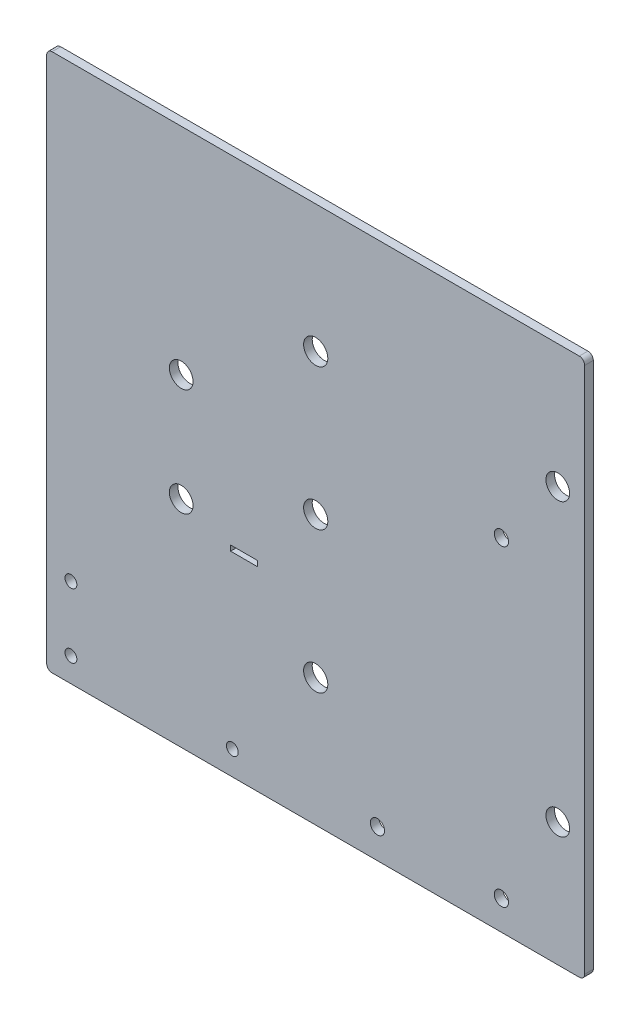
SolidWorks part; units mm, degrees
material "FR4_stuffedProtoboard"
ref_plane "Front Plane" through (0, 0, 0) normal (0, 0, 1) x (1, 0, 0)
ref_plane "Top Plane" through (0, 0, 0) normal (0, 1, 0) x (1, 0, 0)
ref_plane "Right Plane" through (0, 0, 0) normal (1, 0, 0) x (0, 0, -1)
sketch "Sketch1" plane through (0, 0, 0) normal (0, 0, 1) x (1, 0, 0)
  line L1 (-50, -50) -> (50, -50)
  line L2 (-50, -50) -> (-50, 50)
  line L3 (-50, 50) -> (50, 50)
  line L4 (50, -50) -> (50, 50)
  line L5 (-50, -50) -> (50, 50) construction
  line L6 (-50, 50) -> (50, -50) construction
  dimension "D1" = 100
extrude "Boss-Extrude1" add sketch "Sketch1" along normal blind 1.6
sketch "Sketch2" [suppressed] plane through (0, 0, 1.6) normal (0, 0, 1) x (1, 0, 0)
  circle A0 centre (0, 0) radius 50
  line M2 (50, -50) -> (50, 50)
  line M3 (50, 50) -> (-50, 50)
  line M4 (-50, 50) -> (-50, -50)
  line M5 (-50, -50) -> (50, -50)
  dimension "D1" = 100
extrude "Cut-Extrude1" [suppressed] cut sketch "Sketch2" against normal blind 1.6 contours A0 M3 M4 | A0 M4 M5 | A0 M5 M2 | A0 M2 M3
sketch "Sketch3" plane through (0, 0, 0) normal (0, 0, -1) x (-1, 0, 0)
  line L0 (-40, -22) -> (-50, -22) construction
  line L1 (-40, -32) -> (-40, -22) construction
  line L2 (-50, -32) -> (-40, -32) construction
  line L3 (-50, -22) -> (-50, -32) construction
  line L4 (-40, -22) -> (-50, -22)
  line L5 (-40, -32) -> (-40, -22)
  line L6 (-50, -32) -> (-40, -32)
  line L7 (-50, -22) -> (-50, -32)
  line L8 (-40, 22) -> (-40, 32) construction
  line L9 (-40, 32) -> (-50, 32) construction
  line L10 (-50, 32) -> (-50, 22) construction
  line L11 (-50, 22) -> (-40, 22) construction
  line L12 (-40, 22) -> (-40, 32)
  line L13 (-40, 32) -> (-50, 32)
  line L14 (-50, 32) -> (-50, 22)
  line L15 (-50, 22) -> (-40, 22)
  line L16 (5, -22) -> (-5, -22) construction
  line L17 (5, -32) -> (5, -22) construction
  line L18 (-5, -32) -> (5, -32) construction
  line L19 (-5, -22) -> (-5, -32) construction
  line L20 (5, -22) -> (-5, -22)
  line L21 (5, -32) -> (5, -22)
  line L22 (-5, -32) -> (5, -32)
  line L23 (-5, -22) -> (-5, -32)
  line L24 (5, 22) -> (5, 32) construction
  line L25 (5, 32) -> (-5, 32) construction
  line L26 (-5, 32) -> (-5, 22) construction
  line L27 (-5, 22) -> (5, 22) construction
  line L28 (5, 22) -> (5, 32)
  line L29 (5, 32) -> (-5, 32)
  line L30 (-5, 32) -> (-5, 22)
  line L31 (-5, 22) -> (5, 22)
  line L32 (17, 25) -> (45, 25) construction
  line L33 (45, 25) -> (45, -25) construction
  line L34 (17, -25) -> (45, -25) construction
  line L35 (17, 25) -> (17, -25) construction
  line L36 (17, 25) -> (45, 25)
  line L37 (45, 25) -> (45, -25)
  line L38 (17, -25) -> (45, -25)
  line L39 (17, 25) -> (17, -25)
  circle A0 centre (0, 26.25) radius 2.2479 construction
  circle A2 centre (0, 26.25) radius 2.2479
  circle A3 centre (0, 0) radius 2.2479
  circle A4 centre (-34.525, -44.525) radius 1.325 construction
  circle A6 centre (-34.525, -44.525) radius 1.325
  circle A8 centre (0, -26.25) radius 2.2479 construction
  circle A9 centre (0, -26.25) radius 2.2479
  circle A11 centre (-45, -27) radius 2.2
  circle A13 centre (-45, 27) radius 2.2
  circle A14 centre (-34.525, 13.525) radius 1.325 construction
  circle A15 centre (-34.525, 13.525) radius 1.325
  circle A16 centre (15.5, -45.5) radius 1.1 construction
  circle A17 centre (15.5, -45.5) radius 1.1
  circle A18 centre (45.5, -45.5) radius 1.1 construction
  circle A19 centre (45.5, -45.5) radius 1.1
  circle A20 centre (45.5, -33.5) radius 1.1 construction
  circle A21 centre (45.5, -33.5) radius 1.1
  circle A22 centre (-11.475, -44.525) radius 1.325 construction
  circle A23 centre (-11.475, -44.525) radius 1.325
  circle A24 centre (25, -10) radius 2.2 construction
  circle A25 centre (25, -10) radius 2.2
  circle A26 centre (25, 10) radius 2.2 construction
  circle A27 centre (25, 10) radius 2.2
  circle A28 centre (-45, 27) radius 2.2 construction
  circle A29 centre (-45, 27) radius 2.2
  circle A30 centre (-45, -27) radius 2.2 construction
  circle A31 centre (-45, -27) radius 2.2
  dimension "D1" = 4.4958
extrude "Cut-Extrude2" cut sketch "Sketch3" against normal up to surface (1.6 mm away) contours A11 | A2 | A25 | A27 | A6 | A15 | A13 | A3 | A9 | A23 | A17 | A19 | A21 region at (0, 26.25, 0) region at (45, -27, 0) region at (-25, -10, 0) region at (-25, 10, 0) up to face at (0, 0, 1.6)
sketch "Sketch4" plane through (0, 0, 1.6) normal (0, 0, 1) x (1, 0, 0)
  line L0 (38, -44.25) -> (38, -18.925) construction
  line L5 (38, -44.25) -> (38, -18.925)
  line L6 (11.75, -48) -> (34.25, -48) construction
  line L7 (11.75, -48) -> (34.25, -48)
  line L8 (8, -44.25) -> (8, 13.25) construction
  line L9 (8, -44.25) -> (8, 13.25)
  line L10 (-13.3154, -13.3154) -> (-13.3154, -28.3154) construction
  line L11 (33, -3) -> (33, -48) construction
  line L13 (34.25, 17) -> (11.75, 17)
  line L14 (38, 13.25) -> (38, -18.925)
  line L15 (-48, -48) -> (-13, -48) construction
  line L16 (-48, -48) -> (-13, -48)
  line L17 (-48, -31) -> (-48, -48) construction
  line L18 (-48, -31) -> (-48, -48)
  line L19 (-13, -40.5) -> (-13, -32.5) construction
  line L20 (-13, -40.5) -> (-13, -32.5)
  line L21 (-13, -48) -> (-13, -40.5) construction
  line L22 (-13, -48) -> (-13, -40.5)
  line L23 (-13, -32.5) -> (-13, -31) construction
  line L24 (-13, -32.5) -> (-13, -31)
  line L25 (-13, -31) -> (-48, -31) construction
  line L26 (-13, -31) -> (-48, -31)
  line L27 (-20, -34) -> (-20, -48) construction
  line L28 (-10.8154, -12.8154) -> (-15.8154, -12.8154)
  line L29 (-10.8154, -12.8154) -> (-10.8154, -13.8154)
  line L30 (-10.8154, -13.8154) -> (-15.8154, -13.8154)
  line L31 (-15.8154, -12.8154) -> (-15.8154, -13.8154)
  line L32 (-10.8154, -12.8154) -> (-15.8154, -13.8154) construction
  line L33 (-10.8154, -13.8154) -> (-15.8154, -12.8154) construction
  arc A0 (34.25, -48) -> (38, -44.25) centre (34.25, -44.25) ccw construction
  arc A1 (34.25, -48) -> (38, -44.25) centre (34.25, -44.25) ccw
  arc A2 (8, -44.25) -> (11.75, -48) centre (11.75, -44.25) ccw construction
  arc A3 (8, -44.25) -> (11.75, -48) centre (11.75, -44.25) ccw
  arc A4 (11.75, 17) -> (8, 13.25) centre (11.75, 13.25) ccw construction
  arc A5 (11.75, 17) -> (8, 13.25) centre (11.75, 13.25) ccw
  arc A6 (38, 13.25) -> (34.25, 17) centre (34.25, 13.25) ccw construction
  arc A7 (38, 13.25) -> (34.25, 17) centre (34.25, 13.25) ccw
  spline S1 degree 3 poles (-620.7454, 1875.7318) (1130.7944, -1753.4911) (-1538.0407, 1395.2657) (1751.4585, -929.0571) knots -44.539328 -44.539328 -44.539328 -44.539328 44.800344 44.800344 44.800344 44.800344 only from (-11.0484, -16.3728) to (-13.3154, -13.3154) construction
  spline S3 degree 3 poles (-13.0064, -13.8154) (-13.1119, -13.6503) (-13.2149, -13.4836) (-13.3154, -13.3154) knots 0.845859 0.845859 0.845859 0.845859 1 1 1 1 construction
  text T0 "Raspberry Pi Zero W" font "Century Gothic" height 2
  text T1 "Atheros" font "Century Gothic" height 2
  text T2 "ANTENNA HOLE" font "Century Gothic" height in points 5
  dimension "D5" = 1
  dimension "D1" = 5
  dimension "D2" = 20
  dimension "D3" = 3
  dimension "D4" = 7
  dimension "D6" = 15
  dimension "D7" = 5
fillet "Fillet1" radius 1 4 edges at (-50, -50, 0.8) (-50, 50, 0.8) (50, -50, 0.8) (50, 50, 0.8)
extrude "Cut-Extrude3" cut sketch "Sketch4" against normal up to surface (1.6 mm away) contours L28 L31 L30 L29 region at (-13.3154, -13.3154, 1.6) up to face at (-2.2479, -26.25, 0)
